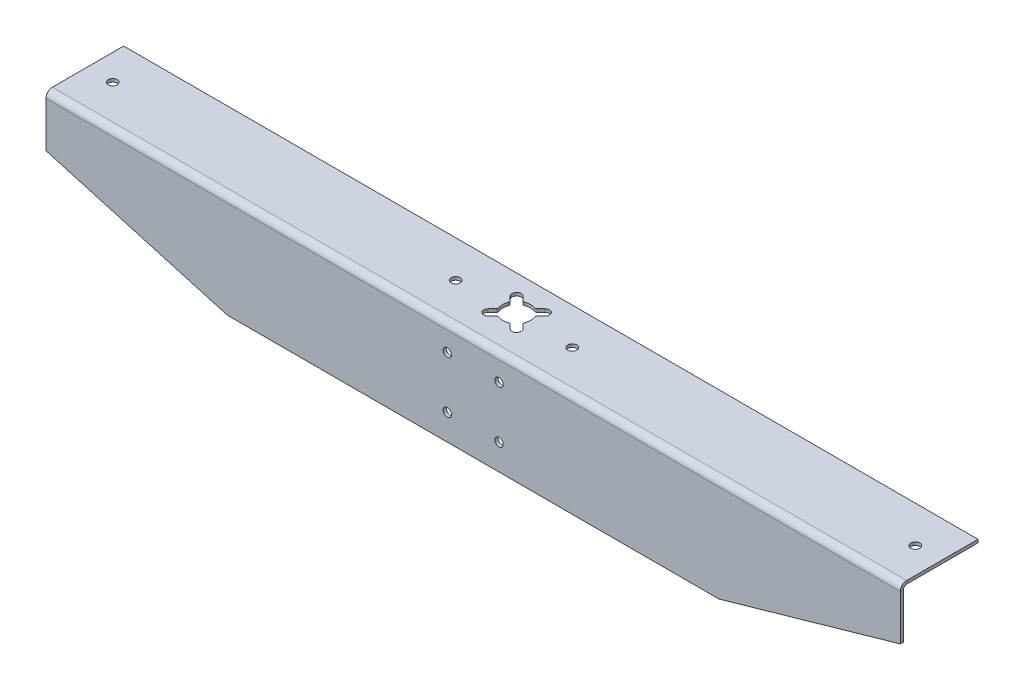
SolidWorks part; units mm, degrees
note: The reader was unsure of these and kept them because the rebuilt part matched: flange length of "Edge-Flange1".
material "1023 Carbon Steel Sheet (SS)"
ref_plane "Front Plane" through (0, 0, 0) normal (0, 0, 1) x (1, 0, 0)
ref_plane "Top Plane" through (0, 0, 0) normal (0, 1, 0) x (1, 0, 0)
ref_plane "Right Plane" through (0, 0, 0) normal (1, 0, 0) x (0, 0, -1)
sketch "Sketch2" plane through (0, 0, 0) normal (0, 0, 1) x (1, 0, 0)
  line L0 (-165, 0) -> (-165, 20)
  line L1 (-95, -20) -> (95, -20)
  line L2 (-165, 20) -> (165, 20)
  line L3 (165, 0) -> (165, 20)
  line L4 (0, 20) -> (0, -20) construction
  line L5 (-165, 0) -> (165, 0) construction
  line L6 (-165, 0) -> (-95, -20)
  line L7 (-10, -10) -> (10, -10) construction
  line L8 (-10, -10) -> (-10, 10) construction
  line L9 (-10, 10) -> (10, 10) construction
  line L10 (10, -10) -> (10, 10) construction
  line L11 (-10, -10) -> (10, 10) construction
  line L12 (-10, 10) -> (10, -10) construction
  line L13 (165, 0) -> (95, -20)
  circle A0 centre (-10, 10) radius 1.6
  circle A1 centre (10, 10) radius 1.6
  circle A2 centre (10, -10) radius 1.6
  circle A3 centre (-10, -10) radius 1.6
  point P0 (0, 0)
  point P1 (0, 0)
  dimension "D3" = 3.2
  dimension "D1" = 330
  dimension "D2" = 40
  dimension "D4" = 20
  dimension "D5" = 20
  dimension "D6" = 70
base flange "Base-Flange1" sketch "Sketch2" thickness 1.2141 reverse thickness direction no parameters "D1"=1.27
edge flange "Edge-Flange1" sketch "Sketch9" flange angle 90 flange length 30 flange position material inside bend radius 1.27 thickness 1.2141 relief rectangular parameters "D6"=10
sketch "Sketch9" plane through (0, 20, -1.2141) normal (0, 1, 0) x (1, 0, 0)
  line L0 (165, 0) -> (-165, 0) construction
  line L1 (165, 0) -> (-165, 0)
  line L2 (-165, 0) -> (-165, 28.7859)
  line L3 (-165, 28.7859) -> (165, 28.7859)
  line L4 (165, 28.7859) -> (165, 0)
bend "EdgeBend1" bend radius 1.27 bend angle 90 parameters "D5"=1
sketch "Sketch10" plane through (0, 20, 0) normal (0, 1, 0) x (1, 0, 0)
  line L0 (0, 30) -> (0, 0) construction
  line L1 (165, 30) -> (-165, 30) construction
  circle A0 centre (0, 16.7859) radius 5.1 construction
  point P5 (0, 10.2828)
  point P6 (6.523, 12.5077)
  point P7 (0, 0)
  point P8 (0, 0)
  point P11 (0, 0)
  line B0 (6.7175, 21.0285) -> (5.1719, 19.4829)
  line B1 (4.2426, 23.5034) -> (2.697, 21.9578)
  line B2 (-4.2426, 23.5034) -> (-2.697, 21.9578)
  line B3 (-6.7175, 21.0285) -> (-5.1719, 19.4829)
  line B4 (6.7175, 12.5432) -> (5.1719, 14.0889)
  line B5 (4.2426, 10.0684) -> (2.697, 11.614)
  line B6 (-4.2426, 10.0684) -> (-2.697, 11.614)
  line B7 (-6.7175, 12.5432) -> (-5.1719, 14.0889)
  arc B8 (6.7175, 21.0285) -> (4.2426, 23.5034) centre (5.4801, 22.266) ccw
  arc B9 (-4.2426, 23.5034) -> (-6.7175, 21.0285) centre (-5.4801, 22.266) ccw
  arc B10 (-6.7175, 12.5432) -> (-4.2426, 10.0684) centre (-5.4801, 11.3058) ccw
  arc B11 (4.2426, 10.0684) -> (6.7175, 12.5432) centre (5.4801, 11.3058) ccw
  arc B12 (-1.9003, 11.7847) -> (1.9003, 11.7847) centre (0, 16.7859) ccw
  arc B13 (-5.0011, 18.6862) -> (-5.0011, 14.8856) centre (0, 16.7859) ccw
  arc B14 (1.9003, 21.787) -> (-1.9003, 21.787) centre (0, 16.7859) ccw
  arc B15 (5.0011, 14.8856) -> (5.0011, 18.6862) centre (0, 16.7859) ccw
  arc B16 (-2.697, 11.614) -> (-1.9003, 11.7847) centre (-2.1667, 11.0836) cw
  arc B17 (-5.0011, 14.8856) -> (-5.1719, 14.0889) centre (-5.7022, 14.6192) cw
  arc B18 (-5.1719, 19.4829) -> (-5.0011, 18.6862) centre (-5.7022, 18.9526) cw
  arc B19 (-1.9003, 21.787) -> (-2.697, 21.9578) centre (-2.1667, 22.4881) cw
  arc B20 (2.697, 21.9578) -> (1.9003, 21.787) centre (2.1667, 22.4881) cw
  arc B21 (5.0011, 18.6862) -> (5.1719, 19.4829) centre (5.7022, 18.9526) cw
  arc B22 (5.1719, 14.0889) -> (5.0011, 14.8856) centre (5.7022, 14.6192) cw
  arc B23 (1.9003, 11.7847) -> (2.697, 11.614) centre (2.1667, 11.0836) cw
sketch_block_instance "Block-TR8x8 POM nut-1"
sketch_block "Block1" parameters "D1"=0.75
extrude "Cut-Extrude1" cut sketch "Sketch10" against normal up to surface (1.2141 mm away) normal cut yes up to face at (0, 18.7859, -16.2421)
sketch "Sketch11" plane through (0, 20, 0) normal (0, 1, 0) x (1, 0, 0)
  line L0 (-156.75, 15.7859) -> (-153.25, 15.7859) construction
  line L1 (-156.75, 18.2859) -> (-156.75, 13.2859) construction
  line L2 (-153.25, 13.2859) -> (-153.25, 18.2859) construction
  line L3 (-24.25, 15.7859) -> (-20.75, 15.7859) construction
  line L4 (-24.25, 18.2859) -> (-24.25, 13.2859) construction
  line L5 (-20.75, 13.2859) -> (-20.75, 18.2859) construction
  line L6 (20.75, 15.7859) -> (24.25, 15.7859) construction
  line L7 (20.75, 18.2859) -> (20.75, 13.2859) construction
  line L8 (24.25, 13.2859) -> (24.25, 18.2859) construction
  line L9 (156.75, 15.7859) -> (153.25, 15.7859) construction
  line L10 (156.75, 13.2859) -> (156.75, 18.2859) construction
  line L11 (153.25, 18.2859) -> (153.25, 13.2859) construction
  circle A0 centre (-155, 15.7859) radius 1.75
  circle A1 centre (-22.5, 15.7859) radius 1.75
  circle A2 centre (22.5, 15.7859) radius 1.75
  circle A3 centre (155, 15.7859) radius 1.75
  dimension "D1" = 3.5
extrude "Cut-Extrude2" cut sketch "Sketch11" against normal up to surface (1.2141 mm away) normal cut yes up to face at (0, 18.7859, -16.7859)
sketch "Bend-Lines1" [suppressed] plane through (0, 0, 0) normal (0, 1, 0) x (1, 0, 0)
sketch "Bounding-Box1" [suppressed] plane through (0, 0, 0) normal (0, 1, 0) x (1, 0, 0)
sheet metal parameters "Sheet-Metal1" thickness 1.2141 parameters "D1"=1.27
flat pattern "Flat-Pattern1" [suppressed]
sketch "Bend-Lines2" plane through (0, 0, 0) normal (0, 1, 0) x (1, 0, 0)
sketch3d "Bounding-Box2" [suppressed]
  line L0 (165, -40, 0) -> (-165, -40, 0) construction
  line L1 (165, 0, 0) -> (-165, 0, 0) construction
  line L2 (165, -40, 0) -> (165, 0, 0) construction
  line L3 (-165, -40, 0) -> (-165, 0, 0) construction
sheet metal parameters "Sheet-Metal2" thickness 1.2141 parameters "D1"=1.27
flat pattern "Flat-Pattern1"
sketch "Bend-Lines2" plane through (0, 0, 0) normal (0, 0, 1) x (1, 0, 0)
  line L0 (165, 18.9901) -> (-165, 18.9901) construction
  line L1 (165, 18.9901) -> (-165, 18.9901) construction
sketch3d "Bounding-Box2" [suppressed]
  line L0 (-165, -20, 0) -> (165, -20, 0) construction
  line L1 (-165, 47.9802, 0) -> (165, 47.9802, 0) construction
  line L2 (-165, -20, 0) -> (-165, 47.9802, 0) construction
  line L3 (165, -20, 0) -> (165, 47.9802, 0) construction
bend of the flat pattern "Flatten-<EdgeBend1>1"
sheet metal parameters "Sheet-Metal3" thickness 1.2141 parameters "D1"=1.27
flat pattern "Flat-Pattern1"
sketch "Bend-Lines2" plane through (0, 0, 0) normal (0, 0, 1) x (1, 0, 0)
  line L0 (165, 18.9901) -> (-165, 18.9901) construction
  line L1 (165, 18.9901) -> (-165, 18.9901) construction
sketch3d "Bounding-Box2" [suppressed]
  line L0 (-165, -20, 0) -> (165, -20, 0) construction
  line L1 (-165, 47.9802, 0) -> (165, 47.9802, 0) construction
  line L2 (-165, -20, 0) -> (-165, 47.9802, 0) construction
  line L3 (165, -20, 0) -> (165, 47.9802, 0) construction
bend of the flat pattern "Flatten-<EdgeBend1>1"
sheet metal parameters "Sheet-Metal4" thickness 1.2141 parameters "D1"=1.27
flat pattern "Flat-Pattern1"
sketch "Bend-Lines2" plane through (0, 0, 0) normal (0, 0, 1) x (1, 0, 0)
  line L0 (165, 18.9901) -> (-165, 18.9901) construction
  line L1 (165, 18.9901) -> (-165, 18.9901) construction
sketch3d "Bounding-Box2" [suppressed]
  line L0 (-165, -20, 0) -> (165, -20, 0) construction
  line L1 (-165, 47.9802, 0) -> (165, 47.9802, 0) construction
  line L2 (-165, -20, 0) -> (-165, 47.9802, 0) construction
  line L3 (165, -20, 0) -> (165, 47.9802, 0) construction
bend of the flat pattern "Flatten-<EdgeBend1>1"
